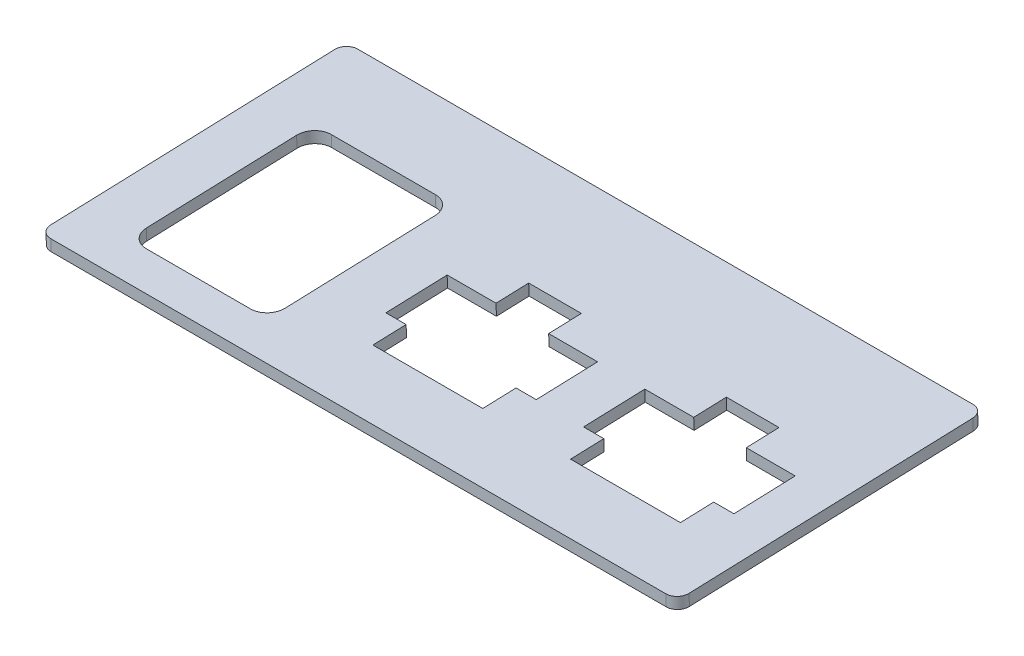
SolidWorks part; units mm, degrees
ref_plane "Front Plane" through (0, 0, 0) normal (0, 0, 1) x (1, 0, 0)
ref_plane "Top Plane" through (0, 0, 0) normal (0, 1, 0) x (1, 0, 0)
ref_plane "Right Plane" through (0, 0, 0) normal (1, 0, 0) x (0, 0, -1)
sketch "Sketch1" plane through (0, -71.9872, -2.5138) normal (0, 0.9994, 0.0349) x (1, 0, 0)
  line L1 (-53.6759, -2.9116) -> (-56.175, -2.9116) construction
  line L2 (56.175, 48.6897) -> (-56.175, 48.6897) construction
  line L8 (-55.175, -4.4116) -> (55.175, -4.4116)
  line L9 (55.175, -4.4116) -> (55.175, 48.6897)
  line L10 (55.175, 48.6897) -> (-55.175, 48.6897)
  line L11 (-55.175, 48.6897) -> (-55.175, -4.4116)
  dimension "D1" = 1.5
  dimension "D2" = 3.0034
  dimension "D3" = 3.0034
extrude "Boss-Extrude1" add sketch "Sketch1" along normal blind 2
sketch "Sketch2" plane through (0, -71.9872, -2.5138) normal (0, -0.9994, -0.0349) x (1, 0, 0)
  line L0 (-4.05, -23.4641) -> (-4.05, -29.1141)
  line L1 (-43.175, -2.1141) -> (-25.175, -2.1141)
  line L2 (-46.175, -5.1141) -> (-46.175, -31.1141)
  line L3 (-43.175, -34.1141) -> (-25.175, -34.1141)
  line L4 (-22.175, -5.1141) -> (-22.175, -31.1141)
  line L5 (-12.5, -12.8641) -> (-9, -12.8641)
  line L6 (-12.5, -12.8641) -> (-12.5, -23.4641)
  line L7 (-12.5, -23.4641) -> (-4.05, -23.4641)
  line L8 (13.5, -12.8641) -> (13.5, -23.4641)
  line L9 (-9, -7.1141) -> (10, -7.1141)
  line L10 (-9, -7.1141) -> (-9, -12.8641)
  line L11 (-4.05, -29.1141) -> (5.05, -29.1141)
  line L12 (10, -7.1141) -> (10, -12.8641)
  line L13 (10, -12.8641) -> (13.5, -12.8641)
  line L14 (5.05, -23.4641) -> (5.05, -29.1141)
  line L15 (5.05, -23.4641) -> (13.5, -23.4641)
  line L16 (-13, -4.6141) -> (14, -31.6141) construction
  line L17 (-13, -4.6141) -> (14, -4.6141) construction
  line L18 (-13, -4.6141) -> (-13, -31.6141) construction
  line L19 (-13, -31.6141) -> (14, -31.6141) construction
  line L20 (14, -4.6141) -> (14, -31.6141) construction
  line L21 (17.5875, 3.7502) -> (17.5875, -36.664) construction
  line L22 (47.675, -18.1641) -> (21.675, -18.1641) construction
  line L23 (34.675, -7.1141) -> (34.675, -29.1141) construction
  line L24 (21.175, -4.6141) -> (21.175, -31.6141) construction
  line L25 (48.175, -31.6141) -> (21.175, -31.6141) construction
  line L26 (48.175, -4.6141) -> (48.175, -31.6141) construction
  line L27 (48.175, -4.6141) -> (21.175, -4.6141) construction
  line L28 (-48.175, -18.1141) -> (-46.175, -18.1141) construction
  line L29 (-48.175, -0.1141) -> (-20.175, -0.1141) construction
  line L30 (-48.175, -0.1141) -> (-48.175, -36.1141) construction
  line L31 (-48.175, -36.1141) -> (-20.175, -36.1141) construction
  line L32 (-20.175, -0.1141) -> (-20.175, -36.1141) construction
  line L33 (-34.175, -2.1141) -> (-34.175, -0.1141) construction
  line L34 (0.5, -7.1141) -> (0.5, -29.1141) construction
  line L35 (-12.5, -18.1641) -> (13.5, -18.1641) construction
  line L36 (48.175, -4.6141) -> (21.175, -31.6141) construction
  line L37 (30.125, -23.4641) -> (21.675, -23.4641)
  line L38 (30.125, -23.4641) -> (30.125, -29.1141)
  line L39 (25.175, -12.8641) -> (21.675, -12.8641)
  line L40 (25.175, -7.1141) -> (25.175, -12.8641)
  line L41 (39.225, -29.1141) -> (30.125, -29.1141)
  line L42 (44.175, -7.1141) -> (44.175, -12.8641)
  line L43 (44.175, -7.1141) -> (25.175, -7.1141)
  line L44 (21.675, -12.8641) -> (21.675, -23.4641)
  line L45 (47.675, -23.4641) -> (39.225, -23.4641)
  line L46 (47.675, -12.8641) -> (47.675, -23.4641)
  line L47 (47.675, -12.8641) -> (44.175, -12.8641)
  line L48 (39.225, -23.4641) -> (39.225, -29.1141)
  line L49 (21.175, -18.1141) -> (14, -18.1141) construction
  line L50 (-55.175, 4.4116) -> (55.175, 4.4116) construction
  line L51 (48.175, -18.1141) -> (52.175, -18.1141) construction
  line L52 (55.175, 4.4116) -> (55.175, -48.6897) construction
  line L53 (-46.7914, -40.6398) -> (46.7914, -40.6398) construction
  line L54 (-13, -18.1141) -> (-20.175, -18.1141) construction
  line L55 (-34.175, -0.1141) -> (-34.175, 4.4116) construction
  line L56 (-34.175, -36.1141) -> (-34.175, -40.6398) construction
  line L57 (-55.175, -48.6897) -> (-55.175, 4.4116) construction
  line L58 (-48.175, -18.1141) -> (-52.175, -18.1141) construction
  arc A0 (-46.175, -31.1141) -> (-43.175, -34.1141) centre (-43.175, -31.1141) ccw
  arc A1 (-25.175, -34.1141) -> (-22.175, -31.1141) centre (-25.175, -31.1141) ccw
  arc A2 (-25.175, -2.1141) -> (-22.175, -5.1141) centre (-25.175, -5.1141) cw
  arc A3 (-43.175, -2.1141) -> (-46.175, -5.1141) centre (-43.175, -5.1141) ccw
  point P28 (0.5, -18.1141)
  point P63 (34.675, -18.1141)
  dimension "D1" = 3
  dimension "D2" = 32
  dimension "D3" = 24
  dimension "D4" = 28
  dimension "D5" = 36
  dimension "D6" = 26
  dimension "D7" = 22
  dimension "D8" = 10.6
  dimension "D9" = 19
  dimension "D10" = 9.1
  dimension "D11" = 5.75
  dimension "D12" = 27
  dimension "D13" = 27
  dimension "D14" = 4
  dimension "D15" = 3
  dimension "D16" = 3
extrude "Cut-Extrude1" cut sketch "Sketch2" against normal up to next
fillet "Fillet1" radius 2 4 edges at (-55.175, -71.1418, 1.93) (55.175, -71.1418, 1.93) (55.175, -69.2886, -51.139) (-55.175, -69.2886, -51.139)
